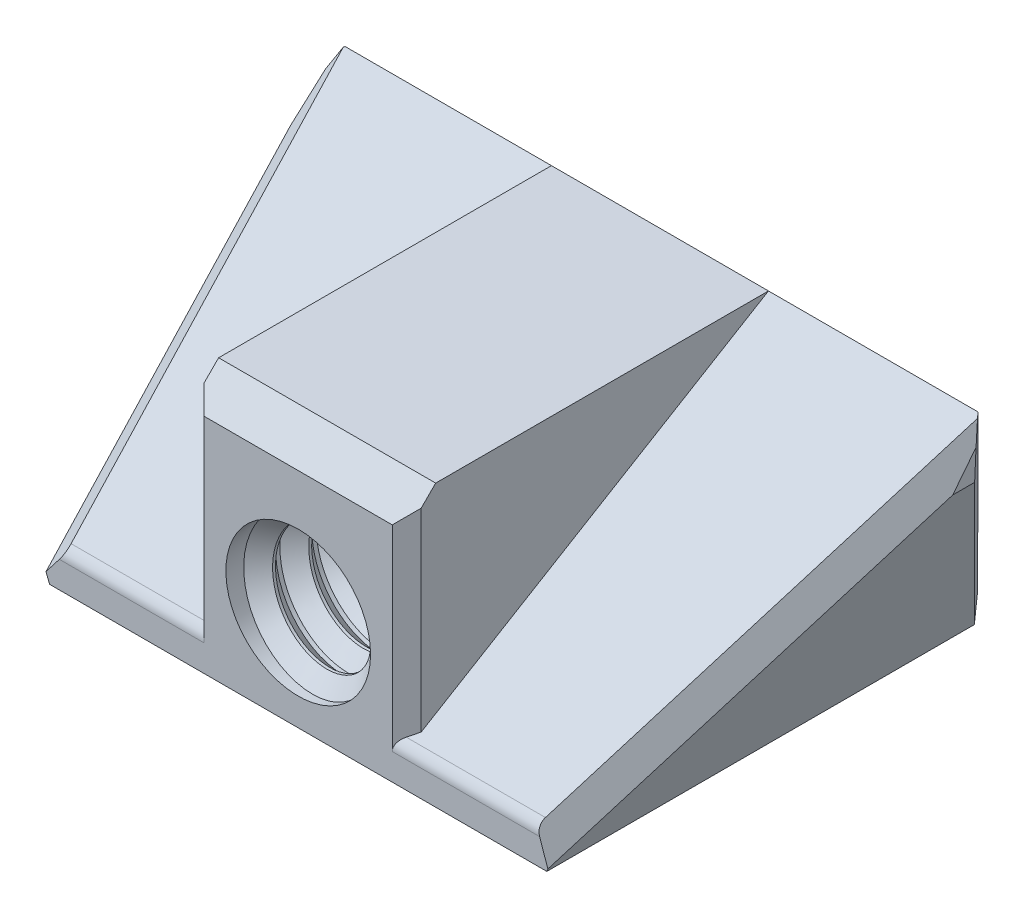
SolidWorks part; units mm, degrees
ref_plane "前视基准面" through (0, 0, 0) normal (0, 0, 1) x (1, 0, 0)
ref_plane "上视基准面" through (0, 0, 0) normal (0, 1, 0) x (1, 0, 0)
ref_plane "右视基准面" through (0, 0, 0) normal (1, 0, 0) x (0, 0, -1)
sketch "草图1" plane through (0, 0, 0) normal (0, 0, 1) x (1, 0, 0)
  line L0 (0, 13.482) -> (0, -13.0025) construction
  line L1 (-7.5, -7.5) -> (7.5, -7.5)
  line L2 (-7.5, -7.5) -> (-7.5, 10.5)
  line L3 (-7.5, 10.5) -> (7.5, 10.5)
  line L4 (7.5, -7.5) -> (7.5, 10.5)
  circle A0 centre (0, 0) radius 5
  dimension "D1" = 10
  dimension "D2" = 18
  dimension "D3" = 15
  dimension "D4" = 7.5
extrude "凸台-拉伸1" add sketch "草图1" along normal blind 25
sketch "草图2" plane through (0, 0, 25) normal (0, 0, 1) x (1, 0, 0)
  circle A0 centre (0, 0) radius 5
curve "螺旋线/涡状线1" pitch 2.5 height 17.5 radius 5 centre (0, 0, 25) axis (0, 0, -1) start towards (1, 0, 0)
sketch "草图3" plane through (0, 0, 0) normal (0, 1, 0) x (1, 0, 0)
  line L0 (5, -25) -> (5, -22.8)
  line L1 (5, -22.8) -> (4, -23.8)
  line L2 (4, -23.8) -> (4, -24)
  line L3 (4, -24) -> (5, -25)
  dimension "D1" = 45
  dimension "D2" = 45
  dimension "D3" = 1
  dimension "D4" = 2.2
sweep "扫描1" add profiles "草图3" path "螺旋线/涡状线1"
sketch "草图4" plane through (7.5, 0, 0) normal (1, 0, 0) x (0, 0, -1)
  line L0 (0, 10.5) -> (-25, -4.5)
  line L1 (-25, -7.5) -> (-25, 10.5) construction
  line L2 (-25, -4.5) -> (-25, -7.5)
  line L3 (-25, -7.5) -> (6.8965, -7.5)
  line L4 (6.8965, -7.5) -> (0, 10.5)
  dimension "D1" = 3
  dimension "D2" = 80
extrude "凸台-拉伸2" add sketch "草图4" along normal blind 15
mirror "镜向1" about plane through (0, 0, 0) normal (1, 0, 0) of "凸台-拉伸2"
sketch "草图6" plane through (0, 0, 25) normal (0, 0, 1) x (1, 0, 0)
  line L0 (0, 104.8936) -> (0, -83.0496) construction
  line L1 (-116.3121, 15) -> (122.695, 15) construction
  line L2 (-20, 41) -> (20, 41) construction
  line L3 (20, 41) -> (30, 15) construction
  line L4 (-20, 41) -> (-30, 15) construction
  line L5 (20, -11) -> (30, 15) construction
  line L6 (-20, -11) -> (20, -11) construction
  line L7 (-20, -11) -> (-30, 15) construction
  line L8 (-61.9686, 11) -> (73.6496, 11) construction
  line L9 (17.1841, -6.9) -> (26.6377, 17.6793)
  line L10 (-17.1841, -6.9) -> (17.1841, -6.9)
  line L11 (-17.1841, -6.9) -> (-24.694, 12.6256)
  line L12 (-24.694, 12.6256) -> (-39.7327, 6.8415)
  line L13 (-39.7327, 6.8415) -> (-26.2223, -28.2856)
  line L14 (-26.2223, -28.2856) -> (27.1118, -28.2856)
  line L15 (27.1118, -28.2856) -> (44.7906, 17.6793)
  line L16 (44.7906, 17.6793) -> (26.6377, 17.6793)
  circle A0 centre (0, 0) radius 4 construction
  point P9 (0, 41)
  dimension "D5" = 8
  dimension "D1" = 52
  dimension "D2" = 40
  dimension "D3" = 60
  dimension "D4" = 11
  dimension "D6" = 30
  dimension "D7" = 4.1
  dimension "D8" = 4.1
  dimension "D9" = 4.1
extrude "切除-拉伸1" cut sketch "草图6" against normal through all
sketch "草图7" plane through (0, 0, 0) normal (0, 0, -1) x (-1, 0, 0)
  line L4 (-7.5, -6.9) -> (7.5, -6.9)
  line L5 (7.5, -6.9) -> (7.5, 10.5)
  line L6 (7.5, 10.5) -> (-7.5, 10.5)
  line L7 (-7.5, 10.5) -> (-7.5, -6.9)
  line L8 (-7.5, -6.9) -> (7.5, -6.9)
  line L9 (7.5, -6.9) -> (7.5, 10.5)
  line L10 (7.5, 10.5) -> (-7.5, 10.5)
  line L11 (-7.5, 10.5) -> (-7.5, -6.9)
  circle A0 centre (0, 0) radius 5 construction
  circle A1 centre (0, 0) radius 5
  dimension "D1" = 0
extrude "凸台-拉伸3" add sketch "草图7" along normal up to surface up to face at (15.4368, 2.8243, -2.9409)
chamfer "倒角1" distance 2 angle 45 5 edges at (0, 10.5, 25) (19.8421, 0.0106, -4.0189) (20.3036, 1.2106, 15.4823) (-20.3036, 1.2106, 15.4823) (-19.8421, 0.0106, -4.0189) first distance on face at (0, 10.5, 12.5) first distance on face at (19.4951, -0.8915, 9.5854) first distance on face at (-15.6214, 3.7843, 11.1929) first distance on face at (0, 5.2553, -2.0094)
chamfer "倒角2" distance 1 angle 45 2 edges at (-7.5, 2, 25) (7.5, 2, 25)
fillet "圆角1" radius 1 2 edges at (11.4941, -4.5, 25) (-11.2842, -4.5, 25)
